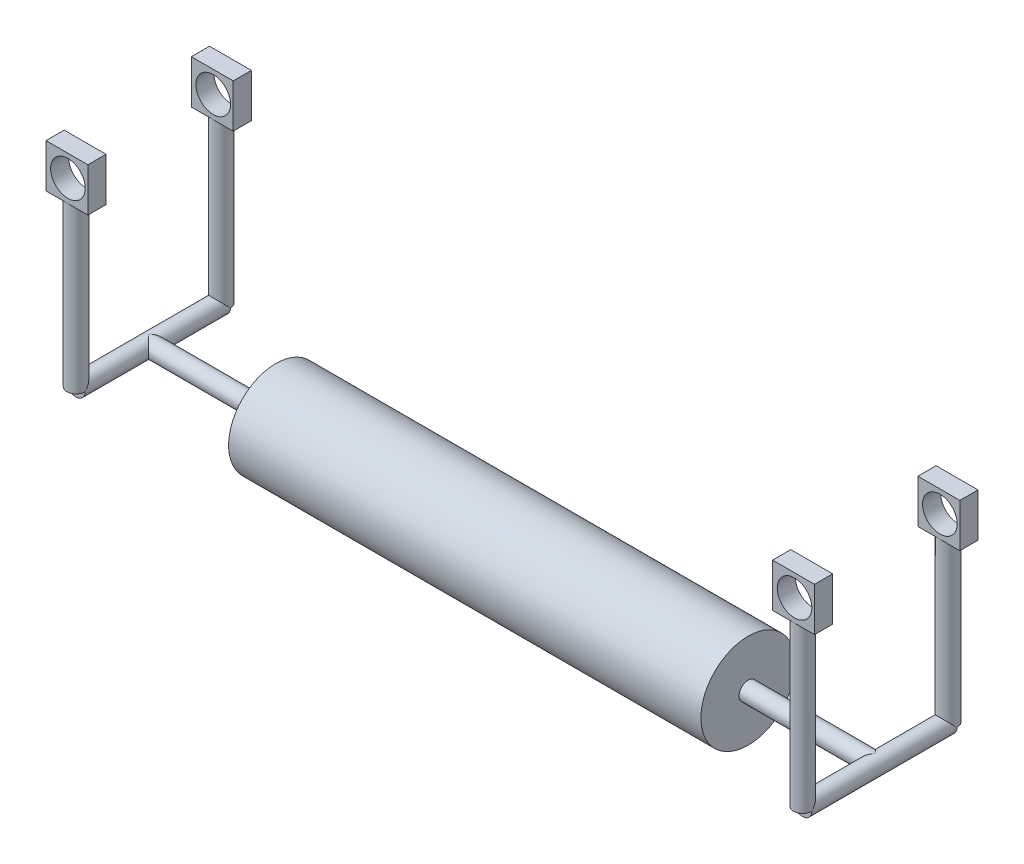
SolidWorks part; units mm, degrees
ref_plane "Front Plane" through (0, 0, 0) normal (0, 0, 1) x (1, 0, 0)
ref_plane "Top Plane" through (0, 0, 0) normal (0, 1, 0) x (1, 0, 0)
ref_plane "Right Plane" through (0, 0, 0) normal (1, 0, 0) x (0, 0, -1)
sketch "Sketch1" plane through (0, 0, 0) normal (1, 0, 0) x (0, 0, -1)
  circle A0 centre (0, 0) radius 13
  dimension "D1" = 26
extrude "Boss-Extrude1" add sketch "Sketch1" along normal blind 65 and the other way blind 65
sketch "Sketch6" plane through (65, 0, 0) normal (1, 0, 0) x (0, 0, -1)
  circle A0 centre (0, 0) radius 2.5
  dimension "D1" = 5
extrude "Boss-Extrude5" add sketch "Sketch6" along normal blind 35
sketch "Sketch7" plane through (-65, 0, 0) normal (-1, 0, 0) x (0, 0, 1)
  circle A0 centre (0, 0) radius 2.5
  dimension "D1" = 5
extrude "Boss-Extrude6" add sketch "Sketch7" along normal blind 35
sketch "Sketch9" plane through (100, 0, 0) normal (1, 0, 0) x (0, 0, -1)
  line L0 (0, 0) -> (0, 2.5)
  circle A0 centre (0, 0) radius 2.5 construction
ref_plane "Plane1" through (0, 0, 0) normal (0, 0, -1) x (0, 1, 0)
sketch "Sketch10" plane through (0, 0, 0) normal (0, 0, -1) x (0, 1, 0)
  circle A0 centre (0, 100) radius 2.5
  dimension "D1" = 5
extrude "Boss-Extrude7" add sketch "Sketch10" along normal blind 20 and the other way blind 20
sketch "Sketch11" plane through (0, 0, 0) normal (0, 1, 0) x (1, 0, 0)
  line L0 (97.5, -20) -> (102.5, -20) construction
  line L1 (102.5, 20) -> (97.5, 20) construction
  circle A0 centre (100, -20) radius 2.5
  circle A1 centre (100, 20) radius 2.5
  dimension "D3" = 5
  dimension "D4" = 5
  dimension "D1" = 0
  dimension "D2" = 0
  dimension "D5" = 2.5
  dimension "D6" = 2.5
extrude "Boss-Extrude8" add sketch "Sketch11" along normal blind 45
sketch "Sketch12" plane through (0, 45, 0) normal (0, 1, 0) x (1, 0, 0)
  line L1 (94.235, -22.5) -> (105.765, -22.5)
  line L2 (94.235, -22.5) -> (94.235, -17.5)
  line L3 (94.235, -17.5) -> (105.765, -17.5)
  line L4 (105.765, -22.5) -> (105.765, -17.5)
  line L5 (94.235, -22.5) -> (105.765, -17.5) construction
  line L6 (94.235, -17.5) -> (105.765, -22.5) construction
  line L7 (105.765, 17.5) -> (94.235, 17.5)
  line L8 (105.765, 17.5) -> (105.765, 22.5)
  line L9 (105.765, 22.5) -> (94.235, 22.5)
  line L10 (94.235, 17.5) -> (94.235, 22.5)
  line L11 (105.765, 17.5) -> (94.235, 22.5) construction
  line L12 (105.765, 22.5) -> (94.235, 17.5) construction
  point P0 (100, -20)
  point P6 (100, 20)
  dimension "D1" = 11.53
  dimension "D2" = 11.53
  dimension "D3" = 5
  dimension "D4" = 5
extrude "Boss-Extrude9" add sketch "Sketch12" along normal blind 12
sketch "Sketch13" plane through (0, 0, -17.5) normal (0, 0, 1) x (1, 0, 0)
  line L0 (94.235, 57) -> (105.765, 57) construction
  line L1 (105.765, 57) -> (105.765, 45) construction
  circle A0 centre (100.265, 51) radius 4.765
  dimension "D1" = 9.53
  dimension "D2" = 6
  dimension "D3" = 5.5
extrude "Cut-Extrude2" cut sketch "Sketch13" against normal blind 12 and the other way blind 66 contours A0
sketch "Sketch14" plane through (0, 0, 0) normal (0, 0, 1) x (1, 0, 0)
  line L0 (-100, 2.5) -> (-100, -2.5) construction
  circle A0 centre (-100, 0) radius 2.5
  dimension "D2" = 5
  dimension "D1" = 0
extrude "Boss-Extrude10" add sketch "Sketch14" along normal blind 20 and the other way blind 20
sketch "Sketch15" plane through (0, 0, 0) normal (0, 1, 0) x (1, 0, 0)
  line L0 (-97.5, 20) -> (-102.5, 20) construction
  line L1 (-102.5, -20) -> (-97.5, -20) construction
  circle A0 centre (-100, 20) radius 2.5
  circle A1 centre (-100, -20) radius 2.5
  dimension "D1" = 5
  dimension "D2" = 5
extrude "Boss-Extrude11" add sketch "Sketch15" along normal blind 45
sketch "Sketch16" plane through (0, 45, 0) normal (0, 1, 0) x (1, 0, 0)
  line L1 (-105.765, -22.5) -> (-94.235, -22.5)
  line L2 (-105.765, -22.5) -> (-105.765, -17.5)
  line L3 (-105.765, -17.5) -> (-94.235, -17.5)
  line L4 (-94.235, -22.5) -> (-94.235, -17.5)
  line L5 (-105.765, -22.5) -> (-94.235, -17.5) construction
  line L6 (-105.765, -17.5) -> (-94.235, -22.5) construction
  line L7 (-105.765, 17.5) -> (-94.235, 17.5)
  line L8 (-105.765, 17.5) -> (-105.765, 22.5)
  line L9 (-105.765, 22.5) -> (-94.235, 22.5)
  line L10 (-94.235, 17.5) -> (-94.235, 22.5)
  line L11 (-105.765, 17.5) -> (-94.235, 22.5) construction
  line L12 (-105.765, 22.5) -> (-94.235, 17.5) construction
  point P0 (-100, -20)
  point P6 (-100, 20)
  dimension "D1" = 5
  dimension "D2" = 11.53
  dimension "D3" = 11.53
  dimension "D4" = 5
extrude "Boss-Extrude12" add sketch "Sketch16" along normal blind 12
sketch "Sketch17" plane through (0, 0, 22.5) normal (0, 0, 1) x (1, 0, 0)
  line L0 (-105.765, 57) -> (-94.235, 57) construction
  line L1 (-94.235, 57) -> (-94.235, 45) construction
  circle A0 centre (-99.735, 51) radius 4.765
  dimension "D3" = 9.53
  dimension "D1" = 6
  dimension "D2" = 5.5
extrude "Cut-Extrude3" cut sketch "Sketch17" against normal blind 51 and the other way blind 12
